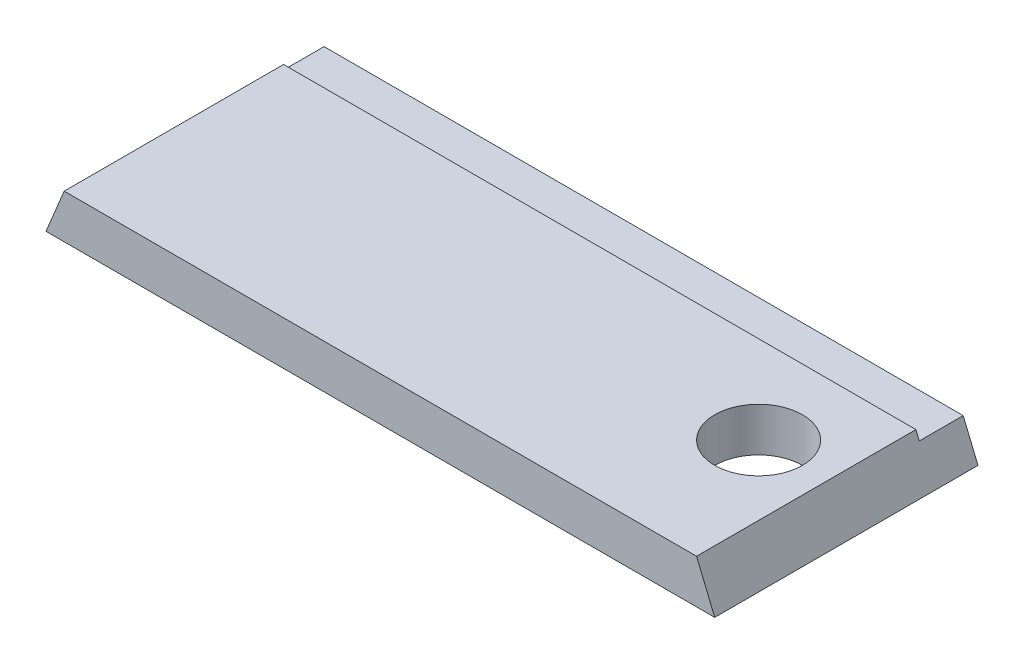
SolidWorks part; units mm, degrees
ref_plane "Front Plane" through (0, 0, 0) normal (0, 0, 1) x (1, 0, 0)
ref_plane "Top Plane" through (0, 0, 0) normal (0, 1, 0) x (1, 0, 0)
ref_plane "Right Plane" through (0, 0, 0) normal (1, 0, 0) x (0, 0, -1)
sketch "Sketch1" plane through (0, 0, 0) normal (0, 0, 1) x (1, 0, 0)
  line L0 (0, 0) -> (193.548, 0)
  line L1 (193.548, 0) -> (188.2875, 12.7)
  line L2 (188.2875, 12.7) -> (5.2605, 12.7)
  line L3 (5.2605, 12.7) -> (0, 0)
  dimension "D1" = 12.7
  dimension "D2" = 193.548
  dimension "D3" = 67.5
  dimension "D4" = 67.5
extrude "Boss-Extrude1" add sketch "Sketch1" along normal blind 76.2
sketch "Sketch2" plane through (0, 12.7, 0) normal (0, 1, 0) x (1, 0, 0)
  line L0 (193.548, -76.2) -> (193.548, 0) construction
  line L1 (193.548, -12.7) -> (0, -12.7)
  line L2 (193.548, -12.7) -> (193.548, 0)
  line L3 (193.548, 0) -> (0, 0)
  line L4 (0, -12.7) -> (0, 0)
  dimension "D1" = 12.7
extrude "Cut-Extrude1" cut sketch "Sketch2" against normal blind 2.3622
sketch "Sketch3" plane through (0, 0, 0) normal (0, -1, 0) x (1, 0, 0)
  line L0 (0, 76.2) -> (193.548, 76.2) construction
  line L1 (193.548, 76.2) -> (193.548, 0) construction
  circle A0 centre (168.148, 38.1) radius 12.7
  dimension "D1" = 25.4
  dimension "D2" = 38.1
  dimension "D3" = 25.4
extrude "Cut-Extrude2" cut sketch "Sketch3" against normal through all
